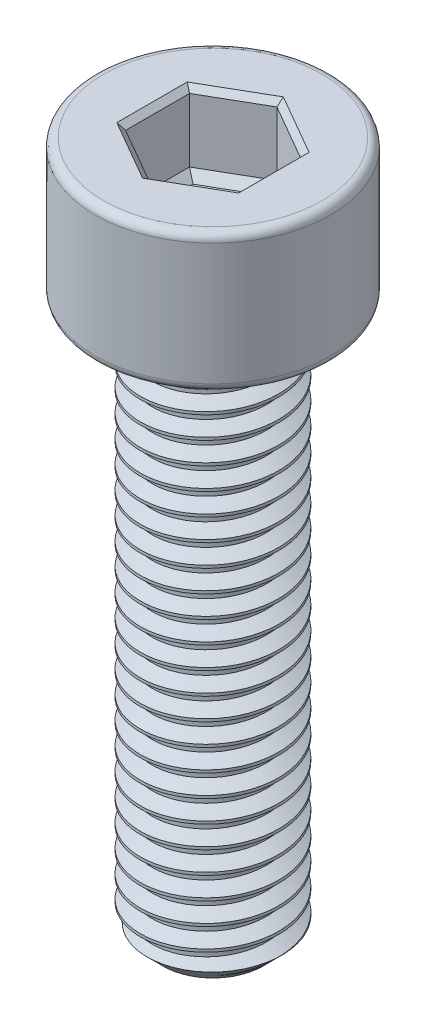
SolidWorks part; units mm, degrees
material "AISI Type A2 Tool Steel"
ref_plane "Front Plane" through (0, 0, 0) normal (0, 0, 1) x (1, 0, 0)
ref_plane "Top Plane" through (0, 0, 0) normal (0, 1, 0) x (1, 0, 0)
ref_plane "Right Plane" through (0, 0, 0) normal (1, 0, 0) x (0, 0, -1)
sketch "Sketch1" plane through (0, 0, 0) normal (0, 1, 0) x (1, 0, 0)
  circle A0 centre (0, 0) radius 2.5
  dimension "D1" = 5
extrude "Boss-Extrude1" add sketch "Sketch1" along normal blind 20
thread "Thread1" pitch 0.8 method cut profile "Thread Profile1" start angle 0, offset 1, length 0, pitch 0.8, diameter 5
ref_plane "Plane1" through (-2.5, 21, 0) normal (0, 0, 1) x (-1, 0, 0)
sketch "Thread Profile1" plane through (-2.5, 21, 0) normal (0, 0, 1) x (-1, 0, 0)
  line L0 (0, 0) -> (0, 0.8) construction
  line L11 (0, 0) -> (0, 0.7)
  line L12 (0, 0.7) -> (-0.433, 0.45)
  line L13 (-0.433, 0.45) -> (-0.433, 0.25)
  line L15 (-0.433, 0.25) -> (0, 0)
  line L17 (-0.433, 0.35) -> (0, 0.35) construction
  point P2 (0, 0)
  dimension "Pitch" = 0.8
  dimension "Profile_Angle" = 60
  dimension "Profile_Land" = 0.2
  dimension "Profile_Height" = 0.433
sketch "Sketch5" plane through (0, 20, 0) normal (0, 1, 0) x (1, 0, 0)
  circle A0 centre (0, 0) radius 4.25
  dimension "D1" = 8.5
extrude "Boss-Extrude2" add sketch "Sketch5" along normal blind 5
fillet "Fillet1" radius 0.3 2 edges at (0, 20, 4.25) (0, 25, 4.25)
sketch "Sketch6" plane through (0, 0, 0) normal (0, 0, 1) x (1, 0, 0)
  line L0 (0, 0) -> (0, 0.2882) construction
  line L1 (0, 0) -> (2.51, 0) construction
  line L2 (2.51, 0) -> (2.51, 0.7)
  line L3 (2.51, 0.7) -> (1.81, 0)
  line L4 (1.81, 0) -> (2.51, 0)
  dimension "D1" = 45
  dimension "D2" = 0.7
  dimension "D3" = 2.51
revolve "Cut-Revolve1" cut sketch "Sketch6" angle 360 about L0
sketch "Sketch7" plane through (0, 25, 0) normal (0, 1, 0) x (1, 0, 0)
  line L1 (0, 2.3094) -> (-2, 1.1547)
  line L2 (-2, 1.1547) -> (-2, -1.1547)
  line L3 (-2, -1.1547) -> (0, -2.3094)
  line L4 (0, -2.3094) -> (2, -1.1547)
  line L5 (2, -1.1547) -> (2, 1.1547)
  line L6 (2, 1.1547) -> (0, 2.3094)
  circle A0 centre (0, 0) radius 2 construction
  dimension "D1" = 4
extrude "Cut-Extrude1" cut sketch "Sketch7" against normal blind 2.5
chamfer "Chamfer1" distance 0.2 angle 45 6 edges at (-2, 25, 0) (-1, 25, 1.7321) (1, 25, 1.7321) (2, 25, 0) (1, 25, -1.7321) (-1, 25, -1.7321)
sketch "Sketch8" plane through (0, 22.5, 0) normal (0, 1, 0) x (1, 0, 0)
  line L1 (0, 2.3094) -> (-2, 1.1547)
  line L2 (-2, 1.1547) -> (-2, -1.1547)
  line L3 (-2, -1.1547) -> (0, -2.3094)
  line L4 (0, -2.3094) -> (2, -1.1547)
  line L5 (2, -1.1547) -> (2, 1.1547)
  line L6 (2, 1.1547) -> (0, 2.3094)
  circle A0 centre (0, 0) radius 2 construction
extrude "Cut-Extrude2" cut sketch "Sketch8" against normal blind 0.3 draft 45
